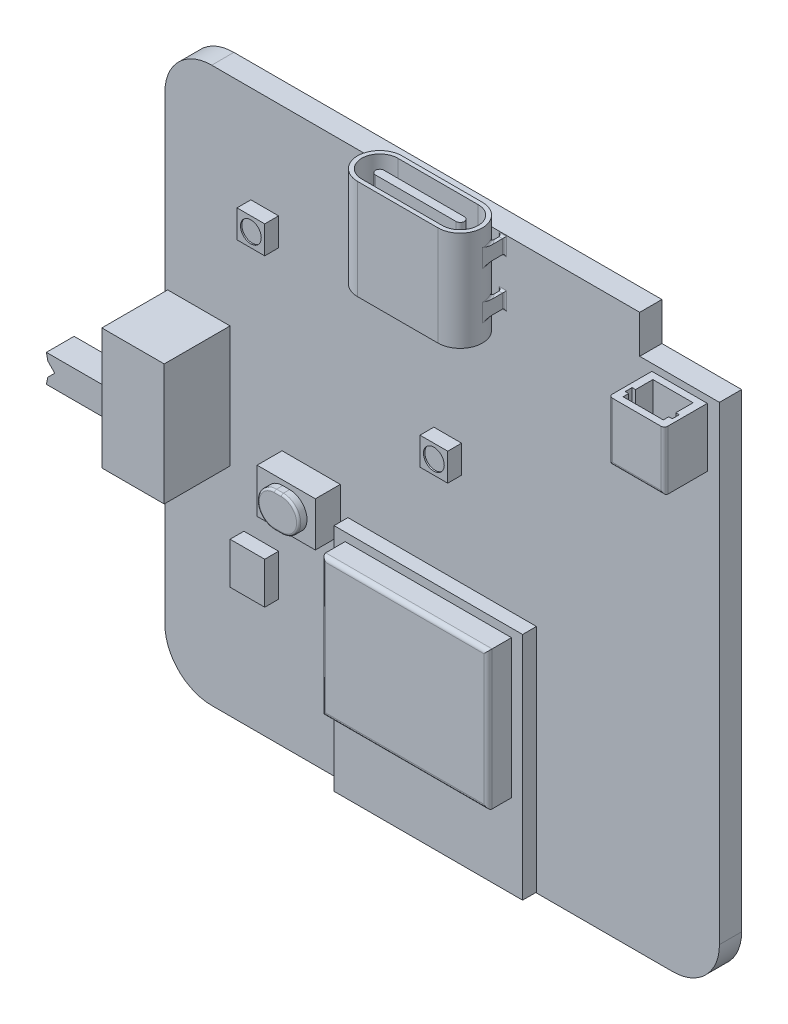
SolidWorks part; units mm, degrees
ref_plane "Front Plane" through (0, 0, 0) normal (0, 0, 1) x (1, 0, 0)
ref_plane "Top Plane" through (0, 0, 0) normal (0, 1, 0) x (1, 0, 0)
ref_plane "Right Plane" through (0, 0, 0) normal (1, 0, 0) x (0, 0, -1)
sketch "PCB Base Sketch" plane through (0, 0, 0) normal (0, 0, 1) x (1, 0, 0)
  line L0 (-16.625, -20) -> (16.625, -20) construction
  line L1 (-20, -16.625) -> (-20, 16.625)
  line L2 (16.625, 20) -> (-16.625, 20) construction
  line L3 (20, -16.625) -> (20, 16.625) construction
  line L4 (-20, 0) -> (20, 0) construction
  line L5 (0, 20) -> (0, -20) construction
  line L6 (20, -16.625) -> (20, 17.25)
  line L7 (20, 17.25) -> (14.25, 17.25)
  line L8 (14.25, 17.25) -> (14.25, 20)
  line L9 (14.25, 20) -> (-16.625, 20)
  line L10 (16.625, -20) -> (6.6, -20)
  line L11 (6.6, -20) -> (6.6, -15)
  line L12 (6.6, -15) -> (-6.6, -15)
  line L13 (-6.6, -15) -> (-6.6, -20)
  line L14 (-6.6, -20) -> (-16.625, -20)
  arc A0 (-16.625, -20) -> (-20, -16.625) centre (-16.625, -16.625) cw
  arc A1 (-20, 16.625) -> (-16.625, 20) centre (-16.625, 16.625) cw
  arc A2 (16.625, -20) -> (20, -16.625) centre (16.625, -16.625) ccw
  arc A3 (16.625, 20) -> (20, 16.625) centre (16.625, 16.625) cw construction
  point P3 (0, -20)
  point P10 (0, 20)
  dimension "D1" = 40
  dimension "D2" = 33.25
  dimension "D3" = 5.75
  dimension "D4" = 2.75
  dimension "D5" = 13.2
  dimension "D6" = 5
extrude "PCB Base" add sketch "PCB Base Sketch" along normal blind 1.6
sketch "ESP32-C3 PCB Sketch" plane through (0, 0, 1.6) normal (0, 0, 1) x (1, 0, 0)
  line L1 (6.8, -3.35) -> (-6.8, -3.35)
  line L2 (6.8, -3.35) -> (6.8, -19.95)
  line L3 (6.8, -19.95) -> (-6.8, -19.95)
  line L4 (-6.8, -3.35) -> (-6.8, -19.95)
  line L5 (6.8, -3.35) -> (-6.8, -19.95) construction
  line L6 (6.8, -19.95) -> (-6.8, -3.35) construction
  line L8 (-16.625, -20) -> (-6.6, -20) construction
  point P0 (0, -11.65)
  dimension "D1" = 13.6
  dimension "D2" = 16.6
  dimension "D3" = 0.05
extrude "ESP32-C3 PCB" add sketch "ESP32-C3 PCB Sketch" along normal blind 1
sketch "ESP32-C3 Sketch" plane through (0, 0, 2.6) normal (0, 0, 1) x (1, 0, 0)
  line L0 (0, -3.35) -> (0, -8.95) construction
  line L1 (-6, -13.95) -> (6, -13.95)
  line L2 (-6, -13.95) -> (-6, -3.95)
  line L3 (-6, -3.95) -> (6, -3.95)
  line L4 (6, -13.95) -> (6, -3.95)
  line L5 (-6, -13.95) -> (6, -3.95) construction
  line L6 (-6, -3.95) -> (6, -13.95) construction
  line L7 (6.8, -3.35) -> (-6.8, -3.35) construction
  line L8 (-6.8, -19.95) -> (6.8, -19.95) construction
  point P0 (0, -8.95)
  dimension "D1" = 12
  dimension "D2" = 10
  dimension "D3" = 6
extrude "ESP32-C3" add sketch "ESP32-C3 Sketch" along normal blind 1.7
fillet "ESP32-C3 Fillets" radius 0.3 4 edges at (-6, -8.95, 4.3) (0, -3.95, 4.3) (6, -8.95, 4.3) (0, -13.95, 4.3)
sketch "JST Battery connector sketch" plane through (0, 0, 1.6) normal (0, 0, 1) x (1, 0, 0)
  line L0 (17.125, 17.25) -> (17.125, 14.625) construction
  line L1 (19.125, 12.5) -> (15.125, 12.5)
  line L2 (19.125, 12.5) -> (19.125, 16.75)
  line L3 (19.125, 16.75) -> (15.125, 16.75)
  line L4 (15.125, 12.5) -> (15.125, 16.75)
  line L5 (19.125, 12.5) -> (15.125, 16.75) construction
  line L6 (19.125, 16.75) -> (15.125, 12.5) construction
  line L7 (20, 17.25) -> (14.25, 17.25) construction
  point P0 (17.125, 14.625)
  dimension "D1" = 4.25
  dimension "D2" = 4
  dimension "D3" = 0.5
extrude "JST Battery connector" add sketch "JST Battery connector sketch" along normal blind 3.1
sketch "JST Connector Inside Sketch" plane through (0, 16.75, 0) normal (0, 1, 0) x (1, 0, 0)
  line L0 (18.825, -3.825) -> (19.125, -3.825) construction
  line L1 (15.675, -3.825) -> (15.675, -4.225)
  line L2 (15.675, -4.225) -> (18.575, -4.225)
  line L3 (18.575, -4.225) -> (18.575, -3.825)
  line L4 (18.575, -3.825) -> (18.825, -3.825)
  line L5 (18.825, -3.825) -> (18.825, -3.325)
  line L6 (15.425, -3.325) -> (15.425, -3.825)
  line L7 (15.425, -3.825) -> (15.675, -3.825)
  line L8 (15.675, -3.825) -> (18.575, -3.825) construction
  line L9 (15.425, -3.825) -> (15.125, -3.825) construction
  line L10 (17.125, -2.075) -> (17.125, -1.6) construction
  line L11 (15.425, -3.325) -> (15.675, -3.325)
  line L12 (15.675, -3.325) -> (15.675, -2.075)
  line L13 (15.675, -2.075) -> (18.575, -2.075)
  line L14 (18.575, -2.075) -> (18.575, -3.325)
  line L15 (18.575, -3.325) -> (18.825, -3.325)
  line L16 (17.125, -1.6) -> (17.125, -4.7) construction
  line L17 (17.125, -4.225) -> (17.125, -4.7) construction
  line L18 (19.125, -4.7) -> (15.125, -4.7) construction
  line L19 (20, -1.6) -> (14.25, -1.6) construction
  line L20 (19.125, -4.7) -> (19.125, -1.6) construction
  line L21 (15.125, -4.7) -> (15.125, -1.6) construction
  point P16 (17.125, -2.075)
  point P17 (17.125, -4.225)
  dimension "D1" = 2.15
  dimension "D2" = 2.9
  dimension "D3" = 0.5
  dimension "D4" = 0.4
  dimension "D5" = 0.25
extrude "JST Connector Inside" cut sketch "JST Connector Inside Sketch" against normal offset from surface (3.25 mm away) 1 up to face at (17.125, 12.5, 3.15)
fillet "JST Connector Fillets" radius 0.25 3 edges at (17.125, 12.5, 4.7) (15.125, 14.625, 4.7) (19.125, 14.625, 4.7)
sketch "USB-C Connector Sketch" plane through (0, 20, 0) normal (0, 1, 0) x (1, 0, 0)
  line L0 (2.9, -3.2) -> (-2.9, -3.2) construction
  line L1 (2.9, -4.8) -> (-2.9, -4.8)
  line L2 (2.9, -1.6) -> (-2.9, -1.6)
  line L3 (14.25, -1.6) -> (-16.625, -1.6) construction
  line L4 (2.9, -3.2) -> (4.5, -3.2) construction
  line L5 (-2.9, -3.2) -> (-4.5, -3.2) construction
  arc A0 (2.9, -4.8) -> (2.9, -1.6) centre (2.9, -3.2) ccw
  arc A1 (-2.9, -1.6) -> (-2.9, -4.8) centre (-2.9, -3.2) ccw
  point P2 (0, -3.2)
  dimension "D1" = 9
  dimension "D2" = 3.2
extrude "USB-C Connector" add sketch "USB-C Connector Sketch" along normal blind 1.2 and the other way blind 6
sketch "USB-C Solder points sketch" plane through (0, 0, 1.6) normal (0, 0, 1) x (1, 0, 0)
  line L1 (-4.25, 19.8) -> (-4.5, 19.8)
  line L2 (-4.25, 19.8) -> (-4.25, 18.8)
  line L3 (-4.25, 18.8) -> (-4.5, 18.8)
  line L4 (-4.5, 19.8) -> (-4.5, 18.8)
  line L5 (-4.25, 19.8) -> (-4.5, 18.8) construction
  line L6 (-4.25, 18.8) -> (-4.5, 19.8) construction
  line L10 (0, 4.3005) -> (0, -2.0131) construction
  line L11 (7.415, 17.6) -> (-7.6457, 17.6) construction
  line L12 (-2.9, 14) -> (-2.9, 21.2) construction
  line L13 (-2.9, 14) -> (-2.9, 21.2) construction
  line L19 (-4.5, 21.2) -> (-4.5, 14) construction
  line L20 (-4.5, 21.2) -> (-4.5, 14) construction
  line L21 (-4.5, 20) -> (-4.5, 18.6) construction
  line L22 (-2.9, 20) -> (-16.625, 20) construction
  line L23 (-4.25, 16.4) -> (-4.5, 15.4) construction
  line L24 (-4.25, 15.4) -> (-4.5, 16.4) construction
  line L25 (-4.5, 15.4) -> (-4.5, 16.4)
  line L26 (-4.25, 16.4) -> (-4.5, 16.4)
  line L27 (-4.25, 15.4) -> (-4.25, 16.4)
  line L28 (-4.25, 15.4) -> (-4.5, 15.4)
  line L29 (4.25, 15.4) -> (4.5, 16.4) construction
  line L30 (4.25, 16.4) -> (4.5, 15.4) construction
  line L31 (4.25, 18.8) -> (4.5, 19.8) construction
  line L32 (4.25, 19.8) -> (4.5, 18.8) construction
  line L33 (4.25, 15.4) -> (4.5, 15.4)
  line L34 (4.25, 15.4) -> (4.25, 16.4)
  line L35 (4.25, 16.4) -> (4.5, 16.4)
  line L36 (4.5, 15.4) -> (4.5, 16.4)
  line L37 (4.5, 19.8) -> (4.5, 18.8)
  line L38 (4.25, 18.8) -> (4.5, 18.8)
  line L39 (4.25, 19.8) -> (4.25, 18.8)
  line L40 (4.25, 19.8) -> (4.5, 19.8)
  point P0 (-4.375, 19.3)
  point P8 (-4.5, 19.3)
  point P11 (-2.9, 17.6)
  point P25 (-4.5, 15.9)
  point P26 (-4.375, 15.9)
  point P35 (4.375, 15.9)
  point P36 (4.5, 15.9)
  point P37 (4.5, 19.3)
  point P38 (4.375, 19.3)
  dimension "D1" = 1
  dimension "D2" = 0.25
  dimension "D3" = 1
extrude "USB-C Solder points" add sketch "USB-C Solder points sketch" along normal up to next
fillet "USB-C Solder point fillets" radius 0.15 24 edges at (4.25, 19.3, 1.6) (4.375, 19.8, 1.6) (4.4362, 19.8, 2.7528) (4.4362, 18.8, 2.7528) (4.375, 18.8, 1.6) (4.5, 19.3, 1.6) (4.25, 15.9, 1.6) (4.375, 15.4, 1.6) (4.5, 15.9, 1.6) (4.375, 16.4, 1.6) (4.4362, 16.4, 2.7528) (4.4362, 15.4, 2.7528) (-4.4362, 15.4, 2.7528) (-4.4362, 16.4, 2.7528) (-4.4362, 18.8, 2.7528) (-4.4362, 19.8, 2.7528) (-4.25, 15.9, 1.6) (-4.375, 15.4, 1.6) (-4.5, 15.9, 1.6) (-4.375, 16.4, 1.6) (-4.25, 19.3, 1.6) (-4.375, 18.8, 1.6) (-4.375, 19.8, 1.6) (-4.5, 19.3, 1.6)
sketch "USB-C Connector Inside Sketch" plane through (0, 21.2, 0) normal (0, 1, 0) x (1, 0, 0)
  line L0 (2.9, -1.9) -> (-2.9, -1.9)
  line L1 (-2.9, -4.5) -> (2.9, -4.5)
  line L2 (2.9, -1.6) -> (-2.9, -1.6)
  line L3 (-2.9, -4.8) -> (2.9, -4.8)
  line L4 (2.9, -1.6) -> (-2.9, -1.6) construction
  line L5 (-2.9, -4.8) -> (2.9, -4.8) construction
  line L6 (2.9, -3.2) -> (-2.9, -3.2) construction
  line L7 (2.9, -3.5) -> (-2.9, -3.5)
  line L8 (2.9, -2.9) -> (-2.9, -2.9)
  arc A0 (-2.9, -1.9) -> (-2.9, -4.5) centre (-2.9, -3.2) ccw
  arc A1 (2.9, -4.5) -> (2.9, -1.9) centre (2.9, -3.2) ccw
  arc A2 (2.9, -4.8) -> (2.9, -1.6) centre (2.9, -3.2) ccw
  arc A3 (-2.9, -1.6) -> (-2.9, -4.8) centre (-2.9, -3.2) ccw
  arc A4 (2.9, -4.8) -> (2.9, -1.6) centre (2.9, -3.2) ccw construction
  arc A5 (-2.9, -1.6) -> (-2.9, -4.8) centre (-2.9, -3.2) ccw construction
  arc A6 (2.9, -3.5) -> (2.9, -2.9) centre (2.9, -3.2) ccw
  arc A7 (-2.9, -2.9) -> (-2.9, -3.5) centre (-2.9, -3.2) ccw
  point P14 (0, -3.2)
  dimension "D3" = 0.6
  dimension "D1" = 0
  dimension "D2" = 0.3
extrude "USB-C Connector Inside" cut sketch "USB-C Connector Inside Sketch" against normal offset from surface (6.2 mm away) 1 up to face at (0, 14, 3.2)
sketch "Connector Inside Cut sketch" plane through (0, 21.2, 0) normal (0, 1, 0) x (1, 0, 0)
  line L2 (2.9, -2.9) -> (-2.9, -2.9)
  line L3 (-2.9, -3.5) -> (2.9, -3.5)
  line L4 (2.9, -2.9) -> (-2.9, -2.9)
  line L5 (-2.9, -3.5) -> (2.9, -3.5)
  arc A2 (2.9, -3.5) -> (2.9, -2.9) centre (2.9, -3.2) ccw
  arc A3 (-2.9, -2.9) -> (-2.9, -3.5) centre (-2.9, -3.2) ccw
  arc A4 (2.9, -3.5) -> (2.9, -2.9) centre (2.9, -3.2) ccw
  arc A5 (-2.9, -2.9) -> (-2.9, -3.5) centre (-2.9, -3.2) ccw
  dimension "D1" = 0
extrude "Connector Inside Cut" cut sketch "Connector Inside Cut sketch" against normal blind 0.25
sketch "Switch Base Sketch" plane through (0, 0, 1.6) normal (0, 0, 1) x (1, 0, 0)
  line L0 (-20, 16.625) -> (-20, -16.625) construction
  line L1 (-19.8, 4.375) -> (-15.3, 4.375)
  line L2 (-19.8, 4.375) -> (-19.8, -4.375)
  line L3 (-19.8, -4.375) -> (-15.3, -4.375)
  line L4 (-15.3, 4.375) -> (-15.3, -4.375)
  line L5 (-19.8, 4.375) -> (-15.3, -4.375) construction
  line L6 (-19.8, -4.375) -> (-15.3, 4.375) construction
  point P0 (-17.55, 0)
  dimension "D1" = 0.2
  dimension "D2" = 4.5
  dimension "D3" = 8.75
extrude "Switch Base" add sketch "Switch Base Sketch" along normal blind 4.75
sketch "Switch well sketch" plane through (-19.8, 0, 0) normal (-1, 0, 0) x (0, 0, 1)
  line L0 (4.35, 4.375) -> (4.35, -4.375) construction
  line L1 (5.35, 2.15) -> (3.35, 2.15)
  line L2 (5.35, 2.15) -> (5.35, -2.15)
  line L3 (5.35, -2.15) -> (3.35, -2.15)
  line L4 (3.35, 2.15) -> (3.35, -2.15)
  line L5 (5.35, 2.15) -> (3.35, -2.15) construction
  line L6 (5.35, -2.15) -> (3.35, 2.15) construction
  line L9 (6.35, 0) -> (1.6, 0) construction
  line L10 (6.35, 4.375) -> (6.35, -4.375) construction
  line L11 (1.6, 16.625) -> (1.6, -16.625) construction
  line L12 (6.35, 4.375) -> (1.6, 4.375) construction
  line L13 (6.35, -4.375) -> (1.6, -4.375) construction
  point P0 (4.35, 0)
  dimension "D1" = 2
  dimension "D2" = 4.3
  dimension "D3" = 1
extrude "Switch well" cut sketch "Switch well sketch" against normal blind 1
sketch "Switch Lever Sketch" plane through (-18.8, 0, 0) normal (-1, 0, 0) x (0, 0, 1)
  line L0 (3.35, -2.15) -> (3.35, -0.15)
  line L1 (3.35, 2.15) -> (3.35, -2.15) construction
  line L2 (3.35, -0.15) -> (5.35, -0.15)
  line L3 (5.35, -2.15) -> (5.35, 2.15) construction
  line L4 (5.35, -0.15) -> (5.35, -2.15)
  line L5 (5.35, -2.15) -> (3.35, -2.15)
  dimension "D1" = 2
extrude "Switch Lever" add sketch "Switch Lever Sketch" along normal offset from surface (6 mm away) 5 up to face at (-19.8, 0, 4.35) offset beyond the face yes
sketch "Lever Grip Sketch" plane through (0, 0, 5.35) normal (0, 0, 1) x (1, 0, 0)
  line L0 (-24.8, -0.15) -> (-24.6937, -0.65)
  line L2 (-24.6937, -0.65) -> (-24.1937, -1.15)
  line L3 (-24.8, -0.15) -> (-24.8, -2.15)
  line L4 (-24.6937, -1.65) -> (-24.1937, -1.15)
  line L5 (-24.8, -1.15) -> (-24.1937, -1.15) construction
  line L6 (-24.8, -0.15) -> (-24.8, -2.15) construction
  line L7 (-24.8, -2.15) -> (-24.6937, -1.65)
  dimension "D1" = 12
  dimension "D2" = 45
  dimension "D3" = 0.5
extrude "Lever Grip" cut sketch "Lever Grip Sketch" against normal up to surface (2 mm away) up to face at (-22.3, -1.15, 3.35)
sketch "Boot Button Base Sketch" plane through (0, 0, 1.6) normal (0, 0, 1) x (1, 0, 0)
  line L0 (-15.3, -4.375) -> (-15.3, 4.375) construction
  line L1 (-7.35, -1.55) -> (-11.55, -1.55)
  line L2 (-7.35, -1.55) -> (-7.35, -4.75)
  line L3 (-7.35, -4.75) -> (-11.55, -4.75)
  line L4 (-11.55, -1.55) -> (-11.55, -4.75)
  line L5 (-7.35, -1.55) -> (-11.55, -4.75) construction
  line L6 (-7.35, -4.75) -> (-11.55, -1.55) construction
  line L7 (6.6, -20) -> (16.625, -20) construction
  point P0 (-9.45, -3.15)
  dimension "D1" = 3.2
  dimension "D2" = 4.2
  dimension "D3" = 3.75
  dimension "D4" = 15.25
extrude "Boot Button Base" add sketch "Boot Button Base Sketch" along normal blind 1.8
sketch "Boot Button Sketch" plane through (0, 0, 3.4) normal (0, 0, 1) x (1, 0, 0)
  line L0 (-9.7, -3.15) -> (-9.2, -3.15) construction
  line L1 (-9.7, -1.9) -> (-9.2, -1.9)
  line L2 (-9.7, -4.4) -> (-9.2, -4.4)
  line L3 (-11.55, -3.15) -> (-7.35, -3.15) construction
  line L4 (-9.45, -1.55) -> (-9.45, -4.75) construction
  line L7 (-11.55, -1.55) -> (-11.55, -4.75)
  line L8 (-11.55, -4.75) -> (-7.35, -4.75)
  line L9 (-7.35, -4.75) -> (-7.35, -1.55)
  line L10 (-7.35, -1.55) -> (-11.55, -1.55)
  line L11 (-11.55, -1.55) -> (-11.55, -4.75) construction
  line L12 (-11.55, -4.75) -> (-7.35, -4.75) construction
  line L13 (-7.35, -4.75) -> (-7.35, -1.55) construction
  line L14 (-7.35, -1.55) -> (-11.55, -1.55) construction
  arc A0 (-9.7, -1.9) -> (-9.7, -4.4) centre (-9.7, -3.15) ccw
  arc A1 (-9.2, -4.4) -> (-9.2, -1.9) centre (-9.2, -3.15) ccw
  point P2 (-9.45, -3.15)
  point P15 (-7.95, -3.15)
  point P20 (-10.95, -3.15)
  dimension "D2" = 2.5
  dimension "D3" = 3
  dimension "D1" = 0
extrude "Boot Button" add sketch "Boot Button Sketch" along normal blind 0.6
fillet "Boot button fillet" radius 0.15 4 edges at (-9.45, -1.9, 4) (-7.95, -3.15, 4) (-9.45, -4.4, 4) (-10.95, -3.15, 4)
sketch "LSM IMU Sketch" plane through (0, 0, 1.6) normal (0, 0, 1) x (1, 0, 0)
  line L0 (-6.8, -3.35) -> (-6.8, -19.95) construction
  line L1 (-14.3, -7.95) -> (-11.8, -7.95)
  line L2 (-14.3, -7.95) -> (-14.3, -10.95)
  line L3 (-14.3, -10.95) -> (-11.8, -10.95)
  line L4 (-11.8, -7.95) -> (-11.8, -10.95)
  line L5 (-14.3, -7.95) -> (-11.8, -10.95) construction
  line L6 (-14.3, -10.95) -> (-11.8, -7.95) construction
  line L7 (-11.55, -4.75) -> (-7.35, -4.75) construction
  point P0 (-13.05, -9.45)
  dimension "D1" = 5
  dimension "D2" = 3
  dimension "D3" = 2.5
  dimension "D4" = 3.2
extrude "LSM IMU" add sketch "LSM IMU Sketch" along normal blind 1
sketch "LEDs Base Sketch" plane through (0, 0, 1.6) normal (0, 0, 1) x (1, 0, 0)
  line L0 (-2.9, 20) -> (-16.625, 20) construction
  line L1 (-11.8, 13) -> (-13.8, 13)
  line L2 (-11.8, 13) -> (-11.8, 11)
  line L3 (-11.8, 11) -> (-13.8, 11)
  line L4 (-13.8, 13) -> (-13.8, 11)
  line L5 (-11.8, 13) -> (-13.8, 11) construction
  line L6 (-11.8, 11) -> (-13.8, 13) construction
  line L7 (1.4, 5.4) -> (-0.6, 5.4)
  line L8 (1.4, 5.4) -> (1.4, 3.4)
  line L9 (1.4, 3.4) -> (-0.6, 3.4)
  line L10 (-0.6, 5.4) -> (-0.6, 3.4)
  line L11 (1.4, 5.4) -> (-0.6, 3.4) construction
  line L12 (1.4, 3.4) -> (-0.6, 5.4) construction
  line L13 (-20, 16.625) -> (-20, -16.625) construction
  line L14 (6.8, -3.35) -> (-6.8, -3.35) construction
  line L15 (-15.3, -4.375) -> (-15.3, 4.375) construction
  point P0 (-12.8, 12)
  point P5 (0.4, 4.4)
  dimension "D1" = 2
  dimension "D2" = 7
  dimension "D3" = 6.2
  dimension "D4" = 6.75
  dimension "D5" = 14.7
extrude "LEDs Base" add sketch "LEDs Base Sketch" along normal blind 1
sketch "LED well sketch" plane through (0, 0, 2.6) normal (0, 0, 1) x (1, 0, 0)
  line L0 (-13.8, 13) -> (-13.8, 11) construction
  line L1 (-13.8, 11) -> (-11.8, 11) construction
  line L2 (-11.8, 11) -> (-11.8, 13) construction
  line L3 (-11.8, 13) -> (-13.8, 13) construction
  line L4 (-0.6, 5.4) -> (-0.6, 3.4) construction
  line L5 (-0.6, 3.4) -> (1.4, 3.4) construction
  line L6 (1.4, 3.4) -> (1.4, 5.4) construction
  line L7 (1.4, 5.4) -> (-0.6, 5.4) construction
  line L8 (-13.8, 13) -> (-13.8, 11) construction
  line L9 (-13.8, 11) -> (-11.8, 11) construction
  line L10 (-11.8, 11) -> (-11.8, 13) construction
  line L11 (-11.8, 13) -> (-13.8, 13) construction
  line L12 (-0.6, 5.4) -> (-0.6, 3.4) construction
  line L13 (-0.6, 3.4) -> (1.4, 3.4) construction
  line L14 (1.4, 3.4) -> (1.4, 5.4) construction
  line L15 (1.4, 5.4) -> (-0.6, 5.4) construction
  line L16 (-13.8, 12) -> (-11.8, 12) construction
  line L17 (-0.6, 4.4) -> (1.4, 4.4) construction
  circle A0 centre (-12.8, 12) radius 0.75
  circle A1 centre (0.4, 4.4) radius 0.75
  point P10 (-12.8, 12)
  point P12 (0.4, 4.4)
  dimension "D1" = 1.5
extrude "LED well" cut sketch "LED well sketch" against normal blind 0.1
